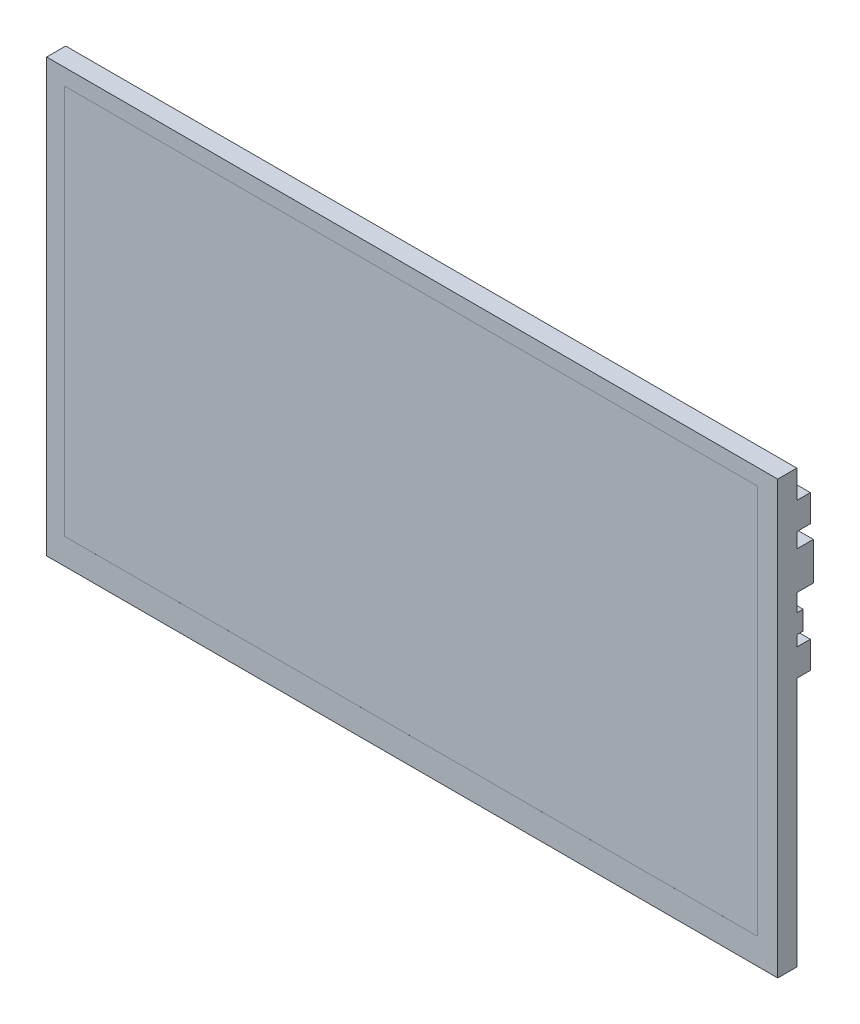
SolidWorks part; units mm, degrees
ref_plane "Front Plane" through (0, 0, 0) normal (0, 0, 1) x (1, 0, 0)
ref_plane "Top Plane" through (0, 0, 0) normal (0, 1, 0) x (1, 0, 0)
ref_plane "Right Plane" through (0, 0, 0) normal (1, 0, 0) x (0, 0, -1)
sketch "Sketch1" plane through (0, 0, 0) normal (0, 0, 1) x (1, 0, 0)
  line L1 (135.185, -79.895) -> (-135.185, -79.895)
  line L2 (135.185, -79.895) -> (135.185, 79.895)
  line L3 (135.185, 79.895) -> (-135.185, 79.895)
  line L4 (-135.185, -79.895) -> (-135.185, 79.895)
  line L5 (135.185, -79.895) -> (-135.185, 79.895) construction
  line L6 (135.185, 79.895) -> (-135.185, -79.895) construction
  point P0 (0, 0)
  dimension "D1" = 270.37
  dimension "D2" = 159.79
extrude "Boss-Extrude1" add sketch "Sketch1" against normal blind 7.05
sketch "Sketch2" plane through (0, 0, 0) normal (0, 0, 1) x (1, 0, 0)
  line L0 (-135.185, 79.895) -> (-135.185, -79.895) construction
  line L1 (127.735, -70.285) -> (-128.585, -70.285)
  line L2 (127.735, -70.285) -> (127.735, 73.895)
  line L3 (127.735, 73.895) -> (-128.585, 73.895)
  line L4 (-128.585, -70.285) -> (-128.585, 73.895)
  line L5 (127.735, -70.285) -> (-128.585, 73.895) construction
  line L6 (127.735, 73.895) -> (-128.585, -70.285) construction
  line L7 (135.185, 79.895) -> (-135.185, 79.895) construction
  point P0 (-0.425, 1.805)
  dimension "D1" = 134.76
  dimension "D2" = 78.09
  dimension "D3" = 144.18
  dimension "D4" = 256.32
extrude "Cut-Extrude1" cut sketch "Sketch2" against normal blind 0.001
sketch "Sketch3" plane through (0, 0, -7.05) normal (0, 0, -1) x (-1, 0, 0)
  line L0 (-135.185, -79.895) -> (-135.185, 79.895) construction
  line L1 (-135.185, 69.545) -> (-110.185, 69.545)
  line L2 (-135.185, 69.545) -> (-135.185, 59.545)
  line L3 (-135.185, 59.545) -> (-110.185, 59.545)
  line L4 (-110.185, 69.545) -> (-110.185, 59.545)
  line L5 (-135.185, 69.545) -> (-110.185, 59.545) construction
  line L6 (-135.185, 59.545) -> (-110.185, 69.545) construction
  line L7 (-135.185, 79.895) -> (135.185, 79.895) construction
  line L9 (-110.185, 40.005) -> (-135.185, 40.005)
  line L10 (-110.185, 40.005) -> (-110.185, 54.005)
  line L11 (-110.185, 54.005) -> (-135.185, 54.005)
  line L12 (-135.185, 40.005) -> (-135.185, 54.005)
  line L13 (-110.185, 40.005) -> (-135.185, 54.005) construction
  line L14 (-110.185, 54.005) -> (-135.185, 40.005) construction
  line L15 (-110.185, 26.525) -> (-135.185, 26.525)
  line L16 (-110.185, 26.525) -> (-110.185, 33.525)
  line L17 (-110.185, 33.525) -> (-135.185, 33.525)
  line L18 (-135.185, 26.525) -> (-135.185, 33.525)
  line L19 (-110.185, 26.525) -> (-135.185, 33.525) construction
  line L20 (-110.185, 33.525) -> (-135.185, 26.525) construction
  line L21 (-110.185, 12.585) -> (-135.185, 12.585)
  line L22 (-110.185, 12.585) -> (-110.185, 22.585)
  line L23 (-110.185, 22.585) -> (-135.185, 22.585)
  line L24 (-135.185, 12.585) -> (-135.185, 22.585)
  line L25 (-110.185, 12.585) -> (-135.185, 22.585) construction
  line L26 (-110.185, 22.585) -> (-135.185, 12.585) construction
  point P4 (-122.685, 64.545)
  point P9 (-122.685, 47.005)
  point P14 (-122.685, 30.025)
  point P19 (-122.685, 17.585)
  line M7 (-135.185, 79.895) -> (-135.185, -79.895)
  dimension "D1" = 15.35
  dimension "D2" = 25
  dimension "D3" = 10
  dimension "D4" = 17.54
  dimension "D5" = 16.98
  dimension "D6" = 12.44
  dimension "D7" = 14
  dimension "D8" = 7
  dimension "D9" = 10
extrude "Boss-Extrude3" add sketch "Sketch3" along normal blind 5 contours L4 L1 L3 M7 region at (122.685, 64.545, -7.05)
extrude "Boss-Extrude4" add sketch "Sketch3<3>" along normal blind 6.12 contours L9 L12 L11 L10
sketch "Sketch3<3>" plane through (0, 0, -7.05) normal (0, 0, -1) x (-1, 0, 0) same geometry as "Sketch3"
extrude "Boss-Extrude5" add sketch "Sketch3<4>" along normal blind 2.35 contours L15 L18 L17 L16
sketch "Sketch3<4>" plane through (0, 0, -7.05) normal (0, 0, -1) x (-1, 0, 0) same geometry as "Sketch3"
extrude "Boss-Extrude6" add sketch "Sketch3<5>" along normal blind 5 contours L22 L23 L21 M7 region at (122.685, 17.585, -7.05)
sketch "Sketch3<5>" plane through (0, 0, -7.05) normal (0, 0, -1) x (-1, 0, 0) same geometry as "Sketch3"
sketch "Sketch5" plane through (0, 0, -13.17) normal (0, 0, -1) x (-1, 0, 0)
  text T0 "AUDIO"
  text T1 "HDMI"
  text T2 "USB"
  text T3 "POWER"
  text T4 "-"
  text T5 "+"
split line "Split Line1"
